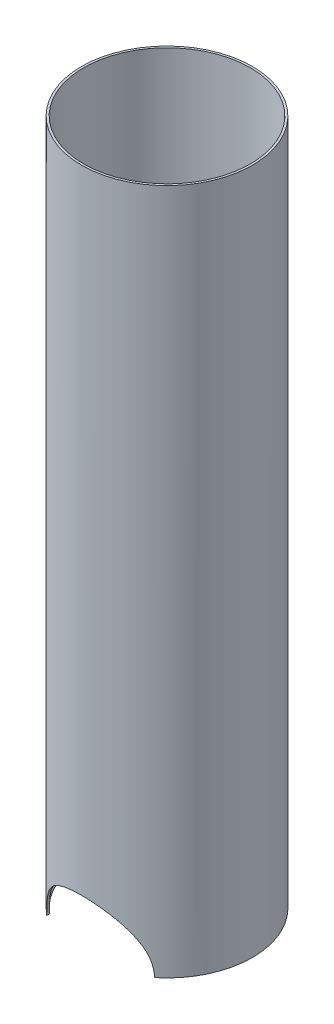
SolidWorks part; units mm, degrees
ref_plane "Front" through (0, 0, 0) normal (0, 0, 1) x (1, 0, 0)
ref_plane "Top" through (0, 0, 0) normal (0, 1, 0) x (1, 0, 0)
ref_plane "Right" through (0, 0, 0) normal (1, 0, 0) x (0, 0, -1)
ref_plane "Plane1" through (0, -110, 0) normal (0, 1, 0) x (1, 0, 0)
sketch "Sketch1" plane through (0, 0, 0) normal (0, 1, 0) x (1, 0, 0)
  circle A0 centre (0, 0) radius 63.5
  circle A1 centre (0, 0) radius 61.9125
  dimension "D1" = 127
  dimension "D2" = 1.5875
extrude "OEM" add sketch "Sketch1" along normal blind 457.2 and the other way blind 152.4
sketch "Sketch3" plane through (0, -110, 0) normal (0, 1, 0) x (1, 0, 0)
  circle A0 centre (0, 0) radius 63.5
  dimension "D1" = 127
extrude "floor" add sketch "Sketch3" along normal blind 1.5875
sketch "Sketch5" plane through (0, 0, 0) normal (0, 0, 1) x (1, 0, 0)
  line L0 (-63.5, -152.4) -> (63.5, -152.4) construction
  line L1 (-40, -152.4) -> (40, -152.4) construction
  arc A0 (40, -152.4) -> (-40, -152.4) centre (0, -152.4) ccw
  dimension "D1" = 40
extrude "eNSR baseplate cutout" cut sketch "Sketch5" against normal through all both and the other way through all
sketch "Sketch6" plane through (0, 0, 0) normal (0, 0, 1) x (1, 0, 0)
  line L0 (63.5, -152.4) -> (63.5, 457.2) construction
  line L1 (-63.5, 457.2) -> (63.5, 457.2)
  line L2 (-63.5, 457.2) -> (-63.5, 357.2)
  line L3 (-63.5, 357.2) -> (63.5, 357.2)
  line L4 (63.5, 457.2) -> (63.5, 357.2)
  dimension "D1" = 100
extrude "too long" cut sketch "Sketch6" against normal through all both and the other way through all
